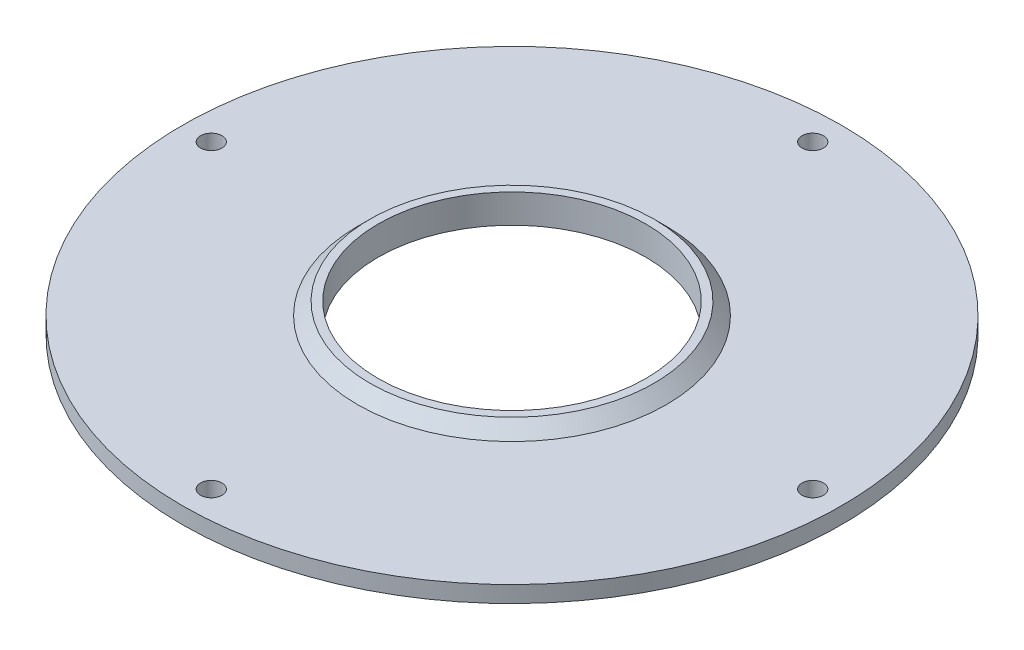
SolidWorks part; units mm, degrees
ref_plane "Front Plane" through (0, 0, 0) normal (0, 0, 1) x (1, 0, 0)
ref_plane "Top Plane" through (0, 0, 0) normal (0, 1, 0) x (1, 0, 0)
ref_plane "Right Plane" through (0, 0, 0) normal (1, 0, 0) x (0, 0, -1)
sketch "Sketch1" plane through (0, 0, 0) normal (0, 1, 0) x (1, 0, 0)
  circle A0 centre (0, 0) radius 80
  circle A1 centre (0, 0) radius 32.5
  dimension "D1" = 160
  dimension "D2" = 65
extrude "Boss-Extrude1" add sketch "Sketch1" along normal blind 4
sketch "Sketch2" plane through (0, 4, 0) normal (0, 1, 0) x (1, 0, 0)
  line L0 (0, 0) -> (0, 73) construction
  line L1 (0, 0) -> (73, 0) construction
  line L2 (0, 0) -> (0, -73) construction
  line L3 (0, 0) -> (-73, 0) construction
  circle A0 centre (0, 73) radius 2.6
  circle A1 centre (0, 0) radius 67.5 construction
  circle A2 centre (73, 0) radius 2.6
  circle A3 centre (0, -73) radius 2.6
  circle A4 centre (-73, 0) radius 2.6
  point P14 (0, 0)
  dimension "D2" = 5.2
  dimension "D3" = 135
  dimension "D1" = 73
  dimension "D4" = 4
extrude "Cut-Extrude1" cut sketch "Sketch2" against normal through all
sketch "Sketch3" plane through (0, 4, 0) normal (0, 1, 0) x (1, 0, 0)
  circle A2 centre (0, 0) radius 34.5
  circle A3 centre (0, 0) radius 32.5
  circle A4 centre (0, 0) radius 32.5
  dimension "D1" = 0
  dimension "D2" = 2
extrude "Boss-Extrude2" add sketch "Sketch3" along normal blind 3
chamfer "Chamfer1" distance 3 angle 45 1 edges at (0, 4, 34.5)
